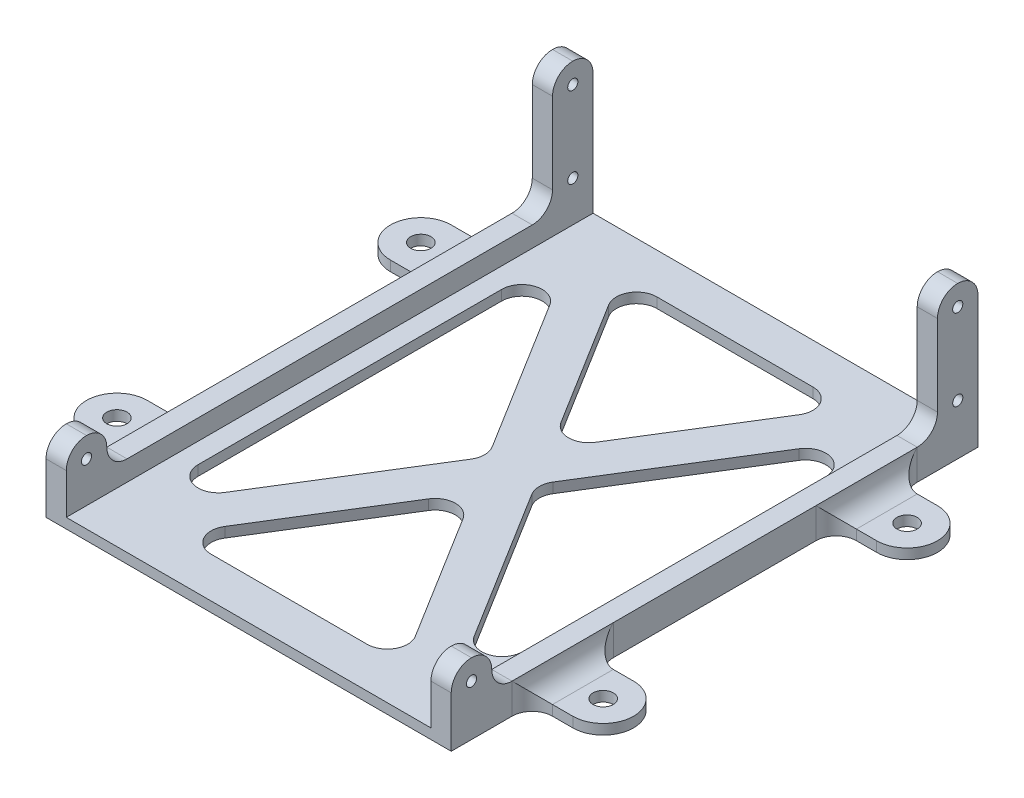
SolidWorks part; units mm, degrees
ref_plane "Front Plane" through (0, 0, 0) normal (0, 0, 1) x (1, 0, 0)
ref_plane "Top Plane" through (0, 0, 0) normal (0, 1, 0) x (1, 0, 0)
ref_plane "Right Plane" through (0, 0, 0) normal (1, 0, 0) x (0, 0, -1)
sketch "Sketch1" plane through (0, 0, 0) normal (0, 1, 0) x (1, 0, 0)
  line L0 (107.95, 78.6193) -> (64.6224, 78.6193) construction
  line L5 (81.5938, 148.4693) -> (32.7062, 148.4693)
  line L6 (107.95, 126.1857) -> (107.95, 31.053)
  line L7 (-6.35, 161.1693) -> (120.65, 161.1693)
  line L8 (-6.35, 161.1693) -> (-6.35, 142.1193)
  line L9 (-6.35, -3.9307) -> (120.65, -3.9307)
  line L10 (120.65, 161.1693) -> (120.65, 142.1193)
  line L11 (81.5938, 8.7693) -> (32.7062, 8.7693)
  line L12 (6.35, 126.1857) -> (6.35, 31.053)
  line L13 (-12.7, 135.7693) -> (-19.05, 135.7693)
  line L15 (-12.7, 116.7193) -> (-19.05, 116.7193)
  line L17 (96.2038, 27.7058) -> (66.6987, 75.2721)
  line L18 (127, 135.7693) -> (133.35, 135.7693)
  line L20 (127, 116.7193) -> (133.35, 116.7193)
  line L22 (127, 40.5193) -> (133.35, 40.5193)
  line L23 (127, 21.4693) -> (133.35, 21.4693)
  line L24 (-12.7, 21.4693) -> (-19.05, 21.4693)
  line L26 (-12.7, 40.5193) -> (-19.05, 40.5193)
  line L27 (-6.35, 110.3693) -> (-6.35, 46.8693)
  line L28 (-6.35, 15.1193) -> (-6.35, -3.9307)
  line L29 (120.65, 15.1193) -> (120.65, -3.9307)
  line L30 (120.65, 110.3693) -> (120.65, 46.8693)
  line L31 (96.2038, 129.5329) -> (66.6987, 81.9666)
  line L32 (86.99, 138.7721) -> (62.5462, 99.3653)
  line L33 (86.99, 18.4666) -> (62.5462, 57.8734)
  line L34 (51.7538, 99.3653) -> (27.31, 138.7721)
  line L35 (49.6776, 78.6193) -> (6.35, 78.6193) construction
  line L36 (47.6013, 81.9666) -> (18.0962, 129.5329)
  line L37 (47.6013, 75.2721) -> (18.0962, 27.7058)
  line L38 (51.7538, 57.8734) -> (27.31, 18.4666)
  arc A0 (-19.05, 135.7693) -> (-19.05, 116.7193) centre (-19.05, 126.2443) ccw
  arc A1 (133.35, 135.7693) -> (133.35, 116.7193) centre (133.35, 126.2443) cw
  arc A2 (133.35, 21.4693) -> (133.35, 40.5193) centre (133.35, 30.9943) ccw
  arc A3 (-19.05, 21.4693) -> (-19.05, 40.5193) centre (-19.05, 30.9943) cw
  arc A4 (120.65, 15.1193) -> (127, 21.4693) centre (127, 15.1193) cw
  arc A5 (120.65, 46.8693) -> (127, 40.5193) centre (127, 46.8693) ccw
  arc A6 (120.65, 110.3693) -> (127, 116.7193) centre (127, 110.3693) cw
  arc A7 (127, 135.7693) -> (120.65, 142.1193) centre (127, 142.1193) cw
  arc A8 (-12.7, 21.4693) -> (-6.35, 15.1193) centre (-12.7, 15.1193) cw
  arc A9 (-12.7, 40.5193) -> (-6.35, 46.8693) centre (-12.7, 46.8693) ccw
  arc A10 (-6.35, 110.3693) -> (-12.7, 116.7193) centre (-12.7, 110.3693) ccw
  arc A11 (-12.7, 135.7693) -> (-6.35, 142.1193) centre (-12.7, 142.1193) ccw
  circle A12 centre (-19.05, 126.2443) radius 3.175
  circle A13 centre (-19.05, 30.9943) radius 3.175
  circle A14 centre (133.35, 30.9943) radius 3.175
  circle A15 centre (133.35, 126.2443) radius 3.175
  arc A16 (6.35, 126.1857) -> (18.0962, 129.5329) centre (12.7, 126.1857) cw
  arc A17 (47.6013, 75.2721) -> (47.6013, 81.9666) centre (42.2051, 78.6193) ccw
  arc A18 (18.0962, 27.7058) -> (6.35, 31.053) centre (12.7, 31.053) cw
  arc A19 (32.7062, 8.7693) -> (27.31, 18.4666) centre (32.7062, 15.1193) cw
  arc A20 (86.99, 18.4666) -> (81.5938, 8.7693) centre (81.5938, 15.1193) cw
  arc A21 (62.5462, 57.8734) -> (51.7538, 57.8734) centre (57.15, 54.5262) ccw
  arc A22 (51.7538, 99.3653) -> (62.5462, 99.3653) centre (57.15, 102.7125) ccw
  arc A23 (32.7062, 148.4693) -> (27.31, 138.7721) centre (32.7062, 142.1193) ccw
  arc A24 (86.99, 138.7721) -> (81.5938, 148.4693) centre (81.5938, 142.1193) ccw
  arc A25 (66.6987, 75.2721) -> (66.6987, 81.9666) centre (72.0949, 78.6193) cw
  arc A26 (107.95, 31.053) -> (96.2038, 27.7058) centre (101.6, 31.053) cw
  arc A27 (96.2038, 129.5329) -> (107.95, 126.1857) centre (101.6, 126.1857) cw
  point P5 (57.15, 76.2)
  point P39 (-6.35, 116.7193)
  point P42 (-6.35, 135.7693)
  point P54 (6.35, 148.4693)
  point P69 (6.35, 8.7693)
  point P72 (21.2949, 8.7693)
  point P75 (93.0051, 8.7693)
  point P78 (57.15, 66.5728)
  point P83 (21.2949, 148.4693)
  point P86 (93.0051, 148.4693)
  point P92 (107.95, 8.7693)
  point P95 (107.95, 148.4693)
  dimension "D5" = 19.05
  dimension "D13" = 9.525
  dimension "D14" = 9.525
  dimension "D15" = 9.525
  dimension "D16" = 6.35
  dimension "D17" = 6.35
  dimension "D18" = 12.7
  dimension "D23" = 6.35
  dimension "D1" = 19.05
  dimension "D2" = 19.05
  dimension "D3" = 127
  dimension "D4" = 165.1
  dimension "D6" = 12.7
  dimension "D7" = 12.7
  dimension "D8" = 19.05
  dimension "D9" = 25.4
  dimension "D10" = 25.4
  dimension "D11" = 25.4
  dimension "D12" = 25.4
  dimension "D19" = 12.7
  dimension "D20" = 12.7
  dimension "D21" = 12.7
  dimension "D22" = 12.7
extrude "Boss-Extrude1" add sketch "Sketch1" along normal blind 3.175
sketch "Sketch2" plane through (0, 3.175, 0) normal (0, 1, 0) x (1, 0, 0)
  line L0 (-6.35, -3.9307) -> (120.65, -3.9307) construction
  line L1 (-6.35, 161.1693) -> (0, 161.1693)
  line L2 (-6.35, 161.1693) -> (-6.35, -3.9307)
  line L3 (-6.35, -3.9307) -> (0, -3.9307)
  line L4 (0, 161.1693) -> (0, -3.9307)
  line L6 (120.65, 161.1693) -> (114.3, 161.1693)
  line L7 (120.65, 161.1693) -> (120.65, -3.9307)
  line L8 (120.65, -3.9307) -> (114.3, -3.9307)
  line L9 (114.3, 161.1693) -> (114.3, -3.9307)
  dimension "D1" = 6.35
  dimension "D2" = 6.35
extrude "Boss-Extrude3" add sketch "Sketch2" along normal blind 6.35
sketch "Sketch3" plane through (0, 9.525, 0) normal (0, 1, 0) x (1, 0, 0)
  line L0 (0, -3.9307) -> (0, 161.1693) construction
  line L1 (-6.35, 161.1693) -> (0, 161.1693)
  line L2 (-6.35, 161.1693) -> (-6.35, 148.4693)
  line L3 (-6.35, 148.4693) -> (0, 148.4693)
  line L4 (0, 161.1693) -> (0, 148.4693)
  line L5 (57.15, 161.1693) -> (57.15, -3.9307) construction
  line L6 (114.3, 161.1693) -> (0, 161.1693) construction
  line L7 (0, -3.9307) -> (114.3, -3.9307) construction
  line L8 (-6.35, 78.6193) -> (120.65, 78.6193) construction
  line L9 (-6.35, 161.1693) -> (-6.35, -3.9307) construction
  line L10 (120.65, -3.9307) -> (120.65, 161.1693) construction
  line L11 (120.65, 148.4693) -> (114.3, 148.4693)
  line L12 (114.3, 161.1693) -> (114.3, 148.4693)
  line L13 (120.65, 161.1693) -> (114.3, 161.1693)
  line L14 (120.65, 161.1693) -> (120.65, 148.4693)
  line L15 (120.65, -3.9307) -> (120.65, 8.7693)
  line L16 (120.65, -3.9307) -> (114.3, -3.9307)
  line L17 (114.3, -3.9307) -> (114.3, 8.7693)
  line L18 (120.65, 8.7693) -> (114.3, 8.7693)
  line L19 (-6.35, 8.7693) -> (0, 8.7693)
  line L20 (0, -3.9307) -> (0, 8.7693)
  line L21 (-6.35, -3.9307) -> (0, -3.9307)
  line L22 (-6.35, -3.9307) -> (-6.35, 8.7693)
  line L23 (0, 148.4693) -> (-6.35, 161.1693) construction
  line L24 (0, 161.1693) -> (-6.35, 148.4693) construction
  line L25 (0, -3.9307) -> (-6.35, 8.7693) construction
  line L26 (0, 8.7693) -> (-6.35, -3.9307) construction
  point P31 (-3.175, 154.8193)
  point P32 (-3.175, 2.4193)
  dimension "D1" = 152.4
extrude "Boss-Extrude4" add sketch "Sketch3" along normal blind 12.7
sketch "Sketch4" plane through (0, 22.225, 0) normal (0, 1, 0) x (1, 0, 0)
  line L0 (0, 148.4693) -> (0, 161.1693) construction
  line L1 (-6.35, 161.1693) -> (0, 161.1693)
  line L2 (-6.35, 161.1693) -> (-6.35, 148.4693)
  line L3 (-6.35, 148.4693) -> (0, 148.4693)
  line L4 (0, 161.1693) -> (0, 148.4693)
  line L6 (114.3, 161.1693) -> (120.65, 161.1693)
  line L7 (114.3, 161.1693) -> (114.3, 148.4693)
  line L8 (114.3, 148.4693) -> (120.65, 148.4693)
  line L9 (120.65, 161.1693) -> (120.65, 148.4693)
  dimension "D1" = 12.7
extrude "Boss-Extrude5" add sketch "Sketch4" along normal blind 25.4
fillet "Fillet1" radius 6.35 12 edges at (117.475, 22.225, -8.7693) (117.475, 22.225, 3.9307) (-3.175, 22.225, 3.9307) (-3.175, 22.225, -8.7693) (117.475, 47.625, -148.4693) (117.475, 47.625, -161.1693) (-3.175, 47.625, -148.4693) (-3.175, 47.625, -161.1693) (117.475, 9.525, -148.4693) (117.475, 9.525, -8.7693) (-3.175, 9.525, -8.7693) (-3.175, 9.525, -148.4693)
fillet "Fillet3" radius 6.35 4 edges at (120.65, 3.175, -30.9943) (120.65, 3.175, -126.2443) (-6.35, 3.175, -30.9943) (-6.35, 3.175, -126.2443)
sketch "Sketch6" plane through (-6.35, 0, 0) normal (-1, 0, 0) x (0, 0, 1)
  line L0 (-161.1693, 0) -> (-142.1193, 0) construction
  line L1 (-161.1693, 41.275) -> (-161.1693, 0) construction
  line L2 (-78.6193, 0) -> (-78.6193, 9.525) construction
  line L3 (-110.3693, 0) -> (-46.8693, 0) construction
  line L4 (-110.3693, 9.525) -> (-46.8693, 9.525) construction
  circle A0 centre (-154.8193, 41.275) radius 1.5875
  circle A1 centre (-154.8193, 15.875) radius 1.5875
  circle A2 centre (-2.4193, 15.875) radius 1.5875
  dimension "D1" = 3.175
  dimension "D5" = 3.175
  dimension "D2" = 41.275
  dimension "D3" = 6.35
  dimension "D4" = 15.875
extrude "Cut-Extrude1" cut sketch "Sketch6" against normal up to surface (127 mm away) up to face at (120.65, 22.4129, -151.3787)
